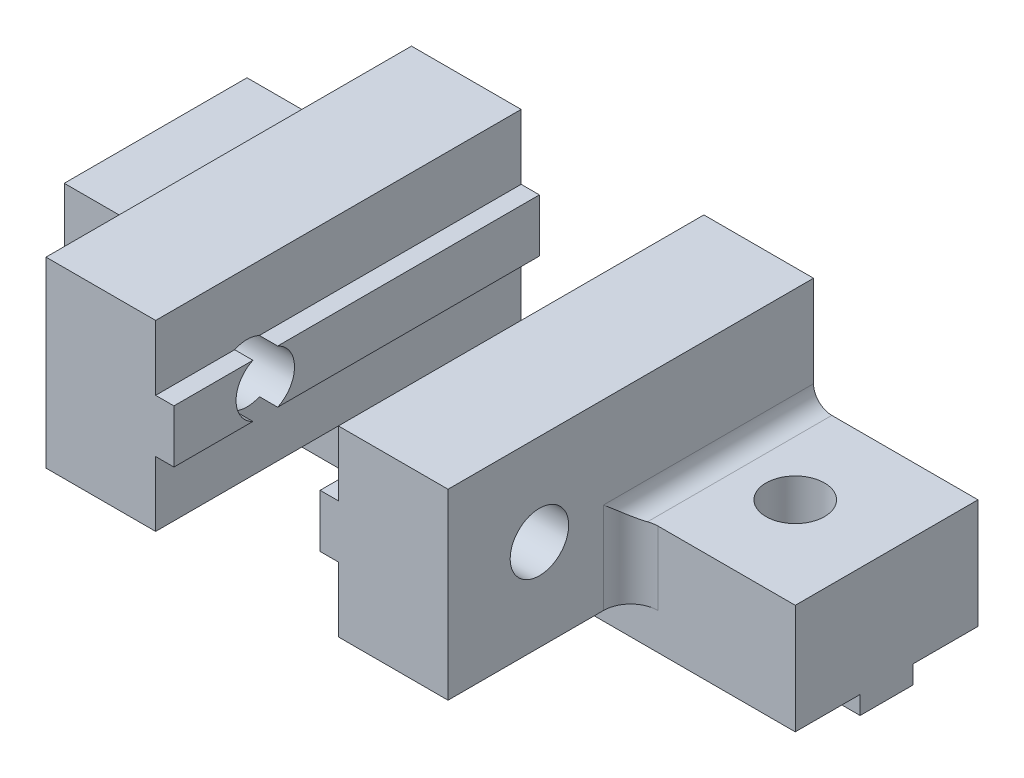
SolidWorks part; units mm, degrees
ref_plane "Front Plane" through (0, 0, 0) normal (0, 0, 1) x (1, 0, 0)
ref_plane "Top Plane" through (0, 0, 0) normal (0, 1, 0) x (1, 0, 0)
ref_plane "Right Plane" through (0, 0, 0) normal (1, 0, 0) x (0, 0, -1)
sketch "Esquisse1" plane through (0, 0, 0) normal (0, 0, 1) x (1, 0, 0)
  line L0 (0, 0) -> (15, 0)
  line L1 (15, 0) -> (15, 6)
  line L2 (15, 6) -> (7, 6)
  line L3 (6, 12) -> (6, 7)
  line L5 (6, 12) -> (0, 12)
  line L6 (0, 12) -> (0, 0)
  arc A0 (7, 6) -> (6, 7) centre (7, 7) cw
  dimension "D1" = 8
  dimension "D2" = 12
  dimension "D3" = 6
  dimension "D4" = 15
extrude "Main" add sketch "Esquisse1" along normal blind 20
sketch "Esquisse4" plane through (0, 0, 0) normal (-1, 0, 0) x (0, 0, 1)
  line L0 (20, 12) -> (0, 12) construction
  line L1 (0, 8.45) -> (20, 8.45)
  line L2 (0, 8.45) -> (0, 5.55)
  line L3 (0, 5.55) -> (20, 5.55)
  line L4 (20, 8.45) -> (20, 5.55)
  line L6 (0, 12) -> (0, 0) construction
  line L7 (20, 12) -> (20, 0) construction
  dimension "D1" = 2.9
  dimension "D2" = 3.55
extrude "VerticalGuidance" add sketch "Esquisse4" along normal blind 1
sketch "Esquisse2" plane through (0, 0, 0) normal (-1, 0, 0) x (0, 0, 1)
  line L0 (20, 12) -> (20, 8.45) construction
  line L1 (20, 12) -> (0, 12) construction
  circle A0 centre (15, 7) radius 1.6
  dimension "D1" = 3.2
  dimension "D2" = 5
  dimension "D3" = 5
extrude "VerticalHole" cut sketch "Esquisse2" against normal through all both and the other way through all
sketch "Esquisse5" plane through (0, 0, 0) normal (0, -1, 0) x (-1, 0, 0)
  line L1 (0, -3.55) -> (-15, -3.55)
  line L2 (0, -3.55) -> (0, -6.45)
  line L3 (0, -6.45) -> (-15, -6.45)
  line L4 (-15, -3.55) -> (-15, -6.45)
  line L8 (0, 0) -> (0, -14.3236) construction
  line L9 (-15, -20) -> (-15, 0) construction
  line L10 (0, 0) -> (-15, 0) construction
  dimension "D1" = 2.9
  dimension "D2" = 3.55
extrude "HorizontalGuidance" add sketch "Esquisse5" along normal blind 1
sketch "Esquisse3" plane through (0, 6, 0) normal (0, -1, 0) x (1, 0, 0)
  line L5 (15, 20) -> (15, 16.249) construction
  line L8 (15, 0) -> (7, 0) construction
  circle A0 centre (10, 5) radius 1.6
  dimension "D1" = 5
  dimension "D2" = 5
  dimension "D3" = 3.2
extrude "HorizontalHole" cut sketch "Esquisse3" against normal through all both and the other way through all
sketch "Esquisse9" plane through (0, 6, 0) normal (0, 1, 0) x (1, 0, 0)
  line L0 (15, -20) -> (15, -16.249) construction
  line L1 (6, -20) -> (15, -20)
  line L2 (6, -20) -> (6, -10)
  line L3 (6, -10) -> (15, -10)
  line L4 (15, -20) -> (15, -10)
  line L5 (15, 0) -> (7, 0) construction
  line L6 (6, -20) -> (6, -16.6) construction
  dimension "D1" = 10
extrude "Enlèv. mat.-Extru.4" cut sketch "Esquisse9" against normal through all both and the other way through all
sketch "Sketch1" plane through (15, 0, 0) normal (1, 0, 0) x (0, 0, -1)
  line L0 (-20, 0) -> (-20, 12) construction
  line L1 (-10, 0) -> (-20, 0)
  line L2 (-10, 0) -> (-10, 2)
  line L3 (-10, 2) -> (-20, 2)
  line L4 (-20, 0) -> (-20, 2)
  point P5 (-19.4957, 2.3752)
  dimension "D1" = 2
extrude "Cut-Extrude1" cut sketch "Sketch1" against normal through all
fillet "Congé2" radius 1.5 1 edges at (6, 4.5, 10)
ref_plane "SymetryPlan" through (-5, 0, 0) normal (1, 0, 0) x (0, 0, -1)
ref_axis "Axe1" through (-5, 0, -4.75) along (0, 0, 1)
mirror "Mirror1" about plane through (-5, 0, 0) normal (1, 0, 0) of bodies 125
